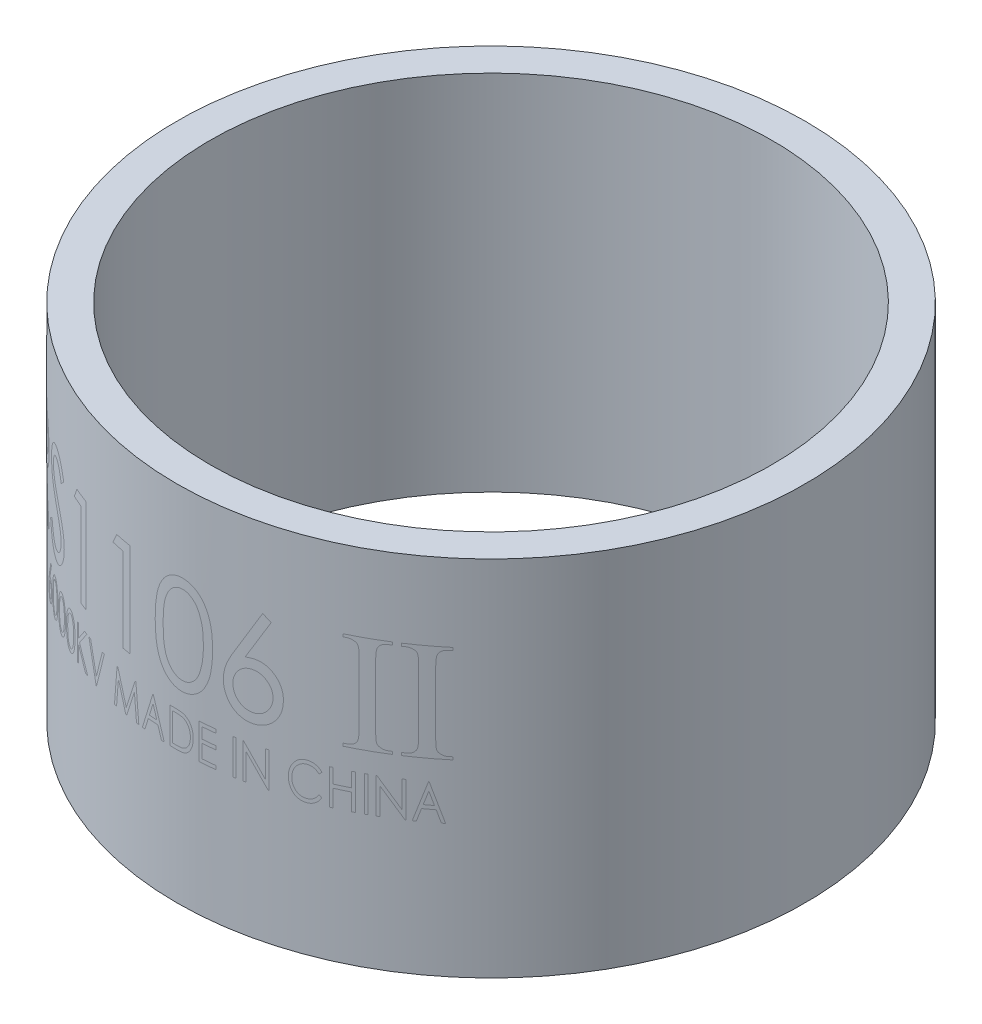
SolidWorks part; units mm, degrees
material "Plain Carbon Steel"
ref_plane "Front Plane" through (0, 0, 0) normal (0, 0, 1) x (1, 0, 0)
ref_plane "Top Plane" through (0, 0, 0) normal (0, 1, 0) x (1, 0, 0)
ref_plane "Right Plane" through (0, 0, 0) normal (1, 0, 0) x (0, 0, -1)
sketch "Sketch1" plane through (0, 0, 0) normal (0, 1, 0) x (1, 0, 0)
  circle A0 centre (0, 0) radius 6.35
  circle A1 centre (0, 0) radius 7.1
  dimension "D1" = 14.2
  dimension "D2" = 12.7
extrude "Boss-Extrude1" add sketch "Sketch1" along normal blind 8.2
sketch "Sketch2" plane through (0, 0, 0) normal (0, 0, 1) x (1, 0, 0)
  line L0 (-7.1, 3) -> (7.1, 3) construction
  line L1 (-7.1, 8.2) -> (-7.1, 0) construction
  line L2 (-7.1, 4.25) -> (3.1, 4.25) construction
  line L3 (7.1, 0) -> (7.1, 8.2) construction
  line L4 (-7.1, 0) -> (7.1, 0) construction
  line L5 (3.1, 4.25) -> (7.1, 4.25) construction
  text T0 "RS1106" font "Century Gothic" height in points 8
  text T1 "II" font "Times New Roman" height in points 9
  text T2 "6000KV MADE IN CHINA" font "Century Gothic" height in points 3
  dimension "D1" = 3
  dimension "D2" = 1.25
  dimension "D3" = 4
wrap "Wrap1" sketch "Sketch2" wrap type scribe source sketch "Sketch2" face at (0, 8.2, 7.1)
